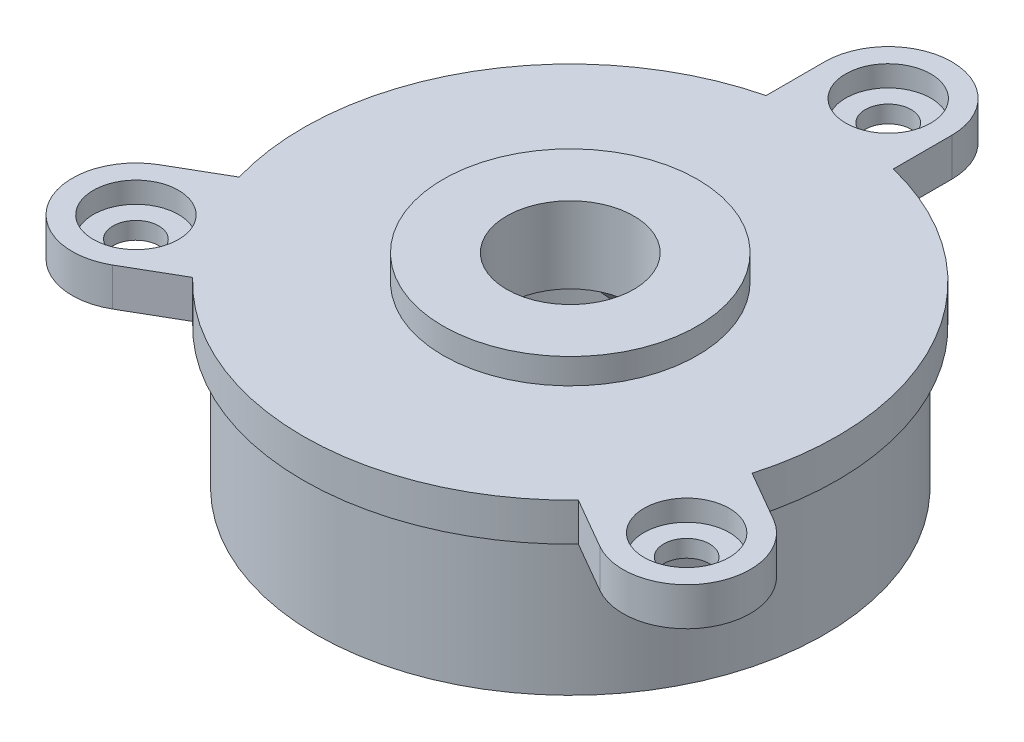
SolidWorks part; units mm, degrees
ref_plane "Front Plane" through (0, 0, 0) normal (0, 0, 1) x (1, 0, 0)
ref_plane "Top Plane" through (0, 0, 0) normal (0, 1, 0) x (1, 0, 0)
ref_plane "Right Plane" through (0, 0, 0) normal (1, 0, 0) x (0, 0, -1)
sketch "Sketch2" plane through (0, 0, 0) normal (0, 1, 0) x (1, 0, 0)
  line L0 (0, 0) -> (0, -50000) construction
  line L1 (5, 25) -> (5, 20.3961)
  line L2 (-5, 25) -> (-5, 20.3961)
  line L3 (24.1506, -8.1699) -> (20.1635, -5.8679)
  line L4 (19.1506, -16.8301) -> (15.1635, -14.5282)
  line L5 (-19.1506, -16.8301) -> (-15.1635, -14.5282)
  line L6 (-24.1506, -8.1699) -> (-20.1635, -5.8679)
  circle A0 centre (0, 0) radius 5
  circle A1 centre (0, 0) radius 10
  circle A2 centre (0, 0) radius 6
  circle A3 centre (0, 0) radius 17
  circle A4 centre (0, 0) radius 20
  circle A5 centre (0, 0) radius 21
  circle A6 centre (0, 0) radius 25 construction
  arc A8 (5, 25) -> (-5, 25) centre (0, 25) ccw
  arc A9 (19.1506, -16.8301) -> (24.1506, -8.1699) centre (21.6506, -12.5) ccw
  arc A10 (-24.1506, -8.1699) -> (-19.1506, -16.8301) centre (-21.6506, -12.5) ccw
  point P14 (-23.7594, -15.9691)
  point P17 (0, 0)
  point P29 (0, 0)
  dimension "D1" = 10
  dimension "D2" = 12
  dimension "D3" = 20
  dimension "D4" = 34
  dimension "D5" = 40
  dimension "D6" = 42
  dimension "D7" = 50
  dimension "D8" = 5
  dimension "D9" = 3
extrude "Boss-Extrude1" add sketch "Sketch2" along normal blind 2 contours A1 A2 | A2 A0 region at (-9.7172, 0, 0) region at (-5.8303, 0, 0)
extrude "Boss-Extrude2" add sketch "Sketch2<3>" against normal blind 3 contours A3 A1 | A4 A3 | A1 A2 | A2 A0 | L6 A10 L5 A5 | L4 A9 L3 A5 | L1 A8 L2 A5 | A5 A4 region at (0, 0, -24.9381) region at (16.0554, 0, -12.5949) region at (21.597, 0, 12.469) region at (-21.597, 0, 12.469) region at (-9.7172, 0, 0) region at (-5.8303, 0, 0) region at (-16.5192, 0, 0) region at (-19.4343, 0, 0)
sketch "Sketch2<3>" plane through (0, 0, 0) normal (0, 1, 0) x (1, 0, 0) same geometry as "Sketch2"
extrude "Boss-Extrude3" add sketch "Sketch2<4>" against normal blind 4 contours A2 A0 region at (-5.8303, 0, 0)
sketch "Sketch2<4>" plane through (0, 0, 0) normal (0, 1, 0) x (1, 0, 0) same geometry as "Sketch2"
extrude "Boss-Extrude4" add sketch "Sketch2<6>" against normal blind 14 contours A4 A3 region at (-19.4343, 0, 0)
sketch "Sketch2<6>" plane through (0, 0, 0) normal (0, 1, 0) x (1, 0, 0) same geometry as "Sketch2"
hole_wizard "CBORE for M12 Hex Head Bolt1" positions "3DSketch1" profile "Sketch3" counterbore size "M12" standard "ANSI Metric" end condition through all
sketch3d "3DSketch1"
  line L0 (0, -3, -25) -> (0, 0, -25) construction
  point P0 (0, 0, -25)
sketch "Sketch3" plane through (0, 0, -25) normal (1, 0, 0) x (0, 0, 1)
  line L0 (0, 0) -> (0, 14)
  line L1 (0, 14) -> (1.8, 14)
  line L3 (1.8, 14) -> (1.8, 1.65)
  line L4 (1.8, 1.65) -> (3.35, 1.65)
  line L5 (3.35, 1.65) -> (3.35, 0)
  line L7 (3.35, 0) -> (0, 0)
  line L11 (0, -6.35) -> (0, 107.95) construction
  dimension "Thru Hole Dia." = 3.6
  dimension "Thru Hole Depth" = 14
  dimension "C'Bore Dia." = 6.7
  dimension "C'Bore Depth" = 1.65
pattern_circular "CirPattern1" count 3 over 360 about axis through (0, 0, 0) along (0, 1, 0) of "CBORE for M12 Hex Head Bolt1"
sketch "Sketch4" plane through (0, 0, 0) normal (0, 0, 1) x (1, 0, 0)
  line L0 (-17, -14) -> (-6, -4)
rib "Rib1" sketch "Sketch4" sketch "Sketch4" thickness 2 extrusion direction parallel to sketch draft on no parameters "D1"=2
pattern_circular "CirPattern2" count 6 over 360 about axis through (0, -14, 0) along (0, 1, 0) of "Rib1"
